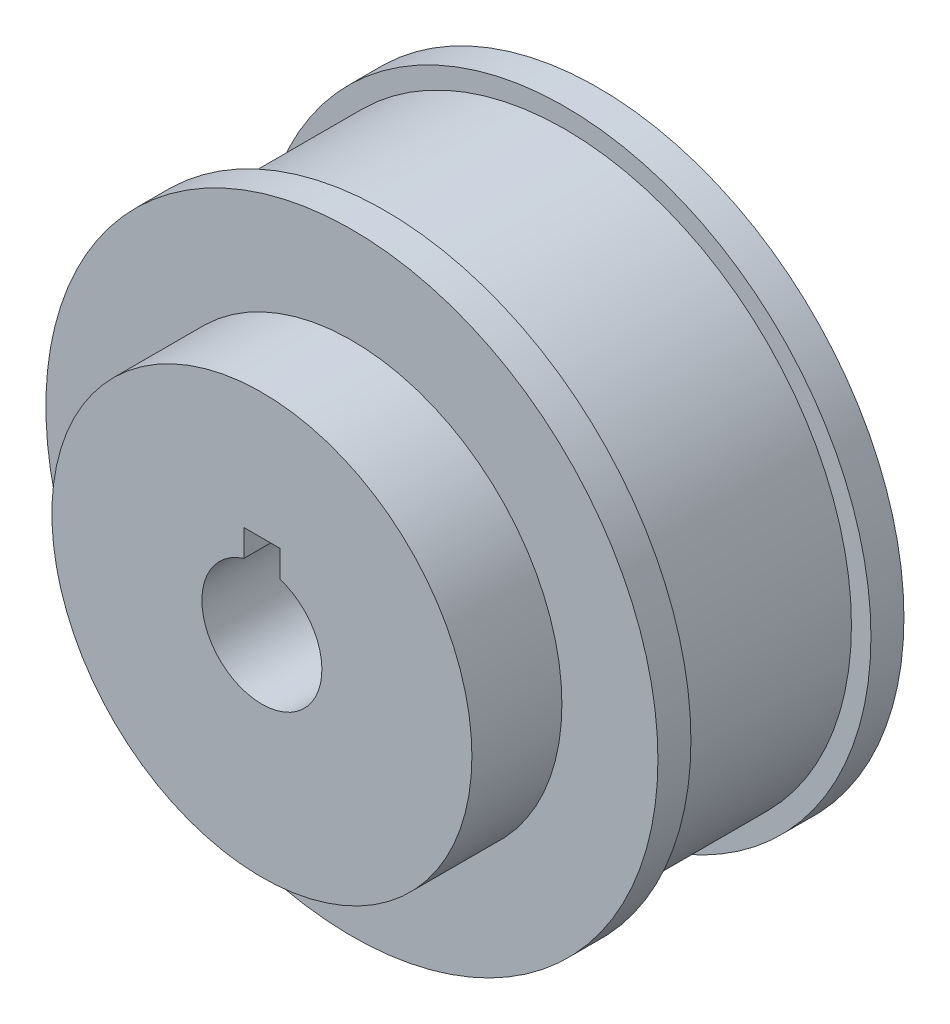
SolidWorks part; units mm, degrees
ref_plane "Płaszczyzna przednia" through (0, 0, 0) normal (0, 0, 1) x (1, 0, 0)
ref_plane "Płaszczyzna górna" through (0, 0, 0) normal (0, 1, 0) x (1, 0, 0)
ref_plane "Płaszczyzna prawa" through (0, 0, 0) normal (1, 0, 0) x (0, 0, -1)
sketch "Szkic1" plane through (0, 0, 0) normal (0, 0, 1) x (1, 0, 0)
  circle A0 centre (0, 0) radius 23.875
extrude "Dodanie-wyciągnięcie1" add sketch "Szkic1" along normal blind 20.5
sketch "Szkic2" plane through (0, 0, 20.5) normal (0, 0, 1) x (1, 0, 0)
  circle A0 centre (0, 0) radius 17.5
extrude "Dodanie-wyciągnięcie2" add sketch "Szkic2" along normal blind 7.5
sketch "Szkic3" plane through (0, 0, 20.5) normal (0, 0, 1) x (1, 0, 0)
  circle A0 centre (0, 0) radius 25.5
extrude "Dodanie-wyciągnięcie3" add sketch "Szkic3" against normal blind 2.75
pattern_linear "Szyk liniowy1" count 2 spacing 17.75 along (0, 0, -1) of "Dodanie-wyciągnięcie3"
sketch "Szkic4" plane through (0, 0, 28) normal (0, 0, 1) x (1, 0, 0)
  circle A0 centre (0, 0) radius 10
extrude "Wytnij-wyciągnięcie1" [suppressed] cut sketch "Szkic4" against normal blind 28
sketch "Szkic5" plane through (0, 0, 28) normal (0, 0, 1) x (1, 0, 0)
  circle A0 centre (0, 0) radius 5
extrude "Wytnij-wyciągnięcie2" cut sketch "Szkic5" against normal blind 30
sketch "Szkic6" plane through (0, 0, 28) normal (0, 0, 1) x (1, 0, 0)
  line L1 (1.5, 0) -> (-1.5, 0)
  line L2 (1.5, 0) -> (1.5, 7)
  line L3 (1.5, 7) -> (-1.5, 7)
  line L4 (-1.5, 0) -> (-1.5, 7)
  line L5 (1.5, 0) -> (-1.5, 7) construction
  line L6 (1.5, 7) -> (-1.5, 0) construction
  point P0 (0, 3.5)
  dimension "D1" = 7
  dimension "D2" = 3
extrude "Wytnij-wyciągnięcie3" cut sketch "Szkic6" against normal blind 40
